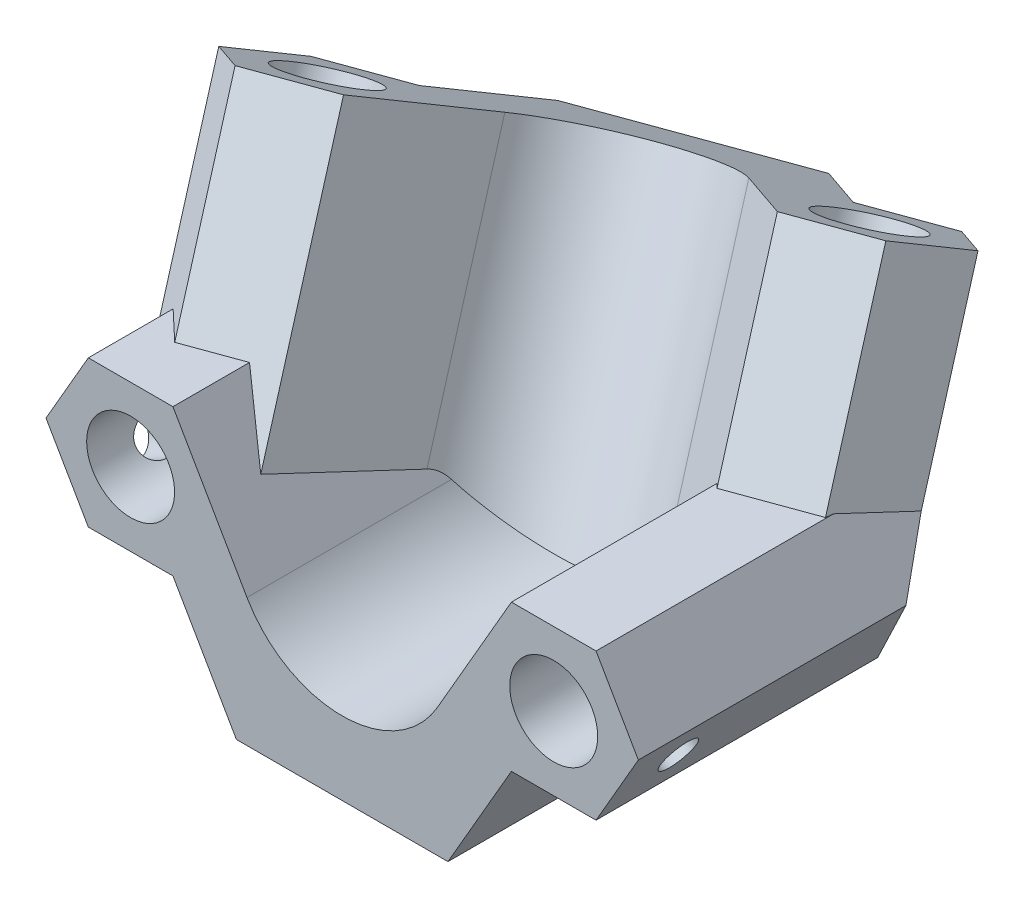
SolidWorks part; units mm, degrees
ref_plane "Front Plane" through (0, 0, 0) normal (0, 0, 1) x (1, 0, 0)
ref_plane "Top Plane" through (0, 0, 0) normal (0, 1, 0) x (1, 0, 0)
ref_plane "Right Plane" through (0, 0, 0) normal (1, 0, 0) x (0, 0, -1)
sketch "Sketch1" plane through (0, 0, 0) normal (0, 1, 0) x (1, 0, 0)
  line L0 (0, 0) -> (0, -10) construction
  line L1 (0, 0) -> (-3.4202, 9.3969) construction
  dimension "D1" = 10
  dimension "D2" = 160
  dimension "D3" = 10
ref_plane "Plane1" through (0, 0, 0) normal (0.9397, 0, -0.342) x (-0.342, 0, -0.9397)
sketch "Sketch2" plane through (0, 0, 0) normal (0.9397, 0, -0.342) x (-0.342, 0, -0.9397)
  line L0 (0, 0) -> (10, 0) construction
  line L1 (0, 0) -> (10, 0) construction
  line L2 (10, 0) -> (10, 17.3205) construction
  line L3 (10, 17.3205) -> (0, 0) construction
  dimension "D1" = 60
  dimension "D2" = 10
sketch "Sketch3" plane through (0, 0, 0) normal (0, 0, 1) x (1, 0, 0)
  line L0 (0, 15) -> (0, -15) construction
  line L1 (13.8564, 6) -> (8.6603, 15) construction
  line L2 (8.6603, 15) -> (0, 15) construction
  line L3 (-8.6603, 15) -> (-13.8564, 6) construction
  line L4 (-13.8564, -6) -> (-8.6603, -15)
  line L5 (-8.6603, -15) -> (8.6603, -15)
  line L6 (8.6603, -15) -> (13.8564, -6)
  line L7 (0, 0) -> (17.3205, 0) construction
  line L8 (13.8564, 6) -> (12.1244, 3) construction
  line L9 (24.2487, 0) -> (20.7846, 6)
  line L10 (20.7846, 6) -> (13.8564, 6)
  line L11 (12.1244, 3) -> (7.7942, -4.5) construction
  line L12 (12.1244, -3) -> (13.8564, -6) construction
  line L13 (13.8564, -6) -> (20.7846, -6)
  line L14 (20.7846, -6) -> (24.2487, 0)
  line L15 (10.3923, 0) -> (12.1244, -3) construction
  line L16 (13.8564, -6) -> (14.3205, -5.1962) construction
  line L17 (15.5205, -3.1177) -> (17.3205, 0) construction
  line L18 (14.3205, -5.1962) -> (15.5205, -3.1177) construction
  line L19 (17.3205, 0) -> (15.5205, 3.1177) construction
  line L20 (15.5205, 3.1177) -> (14.3205, 5.1962) construction
  line L21 (14.3205, 5.1962) -> (13.8564, 6) construction
  line L22 (-13.8564, -6) -> (-20.7846, -6)
  line L23 (-20.7846, -6) -> (-24.2487, 0)
  line L24 (-24.2487, 0) -> (-20.7846, 6)
  line L25 (-20.7846, 6) -> (-13.8564, 6)
  line L26 (-13.8564, 6) -> (-15.5205, 3.1177) construction
  line L27 (-15.5205, 3.1177) -> (-17.3205, 0) construction
  line L28 (-17.3205, 0) -> (-15.5205, -3.1177) construction
  line L29 (-15.5205, -3.1177) -> (-13.8564, -6) construction
  line L30 (-17.3205, 6) -> (-17.3205, -6) construction
  line L31 (-7.7942, -4.5) -> (-13.8564, 6)
  line L32 (7.7942, -4.5) -> (13.8564, 6)
  line L33 (-10.3923, 0) -> (-7.7942, -4.5) construction
  line L34 (0, 15) -> (-8.6603, 15) construction
  line L35 (7.7942, -4.5) -> (10.3923, 0) construction
  line L36 (10.3923, 0) -> (7.7942, -4.5) construction
  circle A0 centre (0, 0) radius 15 construction
  circle A1 centre (17.3205, 0) radius 3.6
  circle A2 centre (17.3205, 0) radius 6 construction
  circle A3 centre (-17.3205, 0) radius 3.6
  arc A4 (-7.7942, -4.5) -> (7.7942, -4.5) centre (0, 0) ccw
  arc A5 (0, 9) -> (-7.7942, -4.5) centre (0, 0) ccw construction
  arc A6 (7.7942, -4.5) -> (0, 9) centre (0, 0) ccw construction
  dimension "D2" = 7.2
  dimension "D4" = 18
  dimension "D1" = 30
  dimension "D3" = 12
extrude "Boss-Extrude1" add sketch "Sketch3" along normal blind 15
ref_plane "Plane2" through (-3.4202, 17.3205, -9.3969) normal (0.171, -0.866, 0.4698) x (-0.9849, -0.1641, 0.056)
sketch "Sketch25" plane through (0, 0, 0) normal (0, 0, -1) x (-1, 0, 0)
  line L0 (-7.7942, -4.5) -> (-13.8564, 6)
  line L1 (-13.8564, 6) -> (-20.7846, 6)
  line L2 (-20.7846, 6) -> (-24.2487, 0)
  line L3 (-24.2487, 0) -> (-20.7846, -6)
  line L4 (-20.7846, -6) -> (-13.8564, -6)
  line L5 (-13.8564, -6) -> (-8.6603, -15)
  line L6 (-8.6603, -15) -> (8.6603, -15)
  line L7 (8.6603, -15) -> (13.8564, -6)
  line L8 (13.8564, -6) -> (20.7846, -6)
  line L9 (20.7846, -6) -> (24.2487, 0)
  line L10 (24.2487, 0) -> (20.7846, 6)
  line L11 (20.7846, 6) -> (13.8564, 6)
  line L12 (13.8564, 6) -> (7.7942, -4.5)
  arc A0 (-7.7942, -4.5) -> (7.7942, -4.5) centre (0, 0) ccw
  arc A1 (-7.7942, -4.5) -> (7.7942, -4.5) centre (0, 0) ccw construction
  arc A2 (7.7942, -4.5) -> (-7.7942, -4.5) centre (0, 0) ccw construction
sketch "Sketch11" plane through (-3.4202, 17.3205, -9.3969) normal (0.171, -0.866, 0.4698) x (-0.9849, -0.1641, 0.056)
  line L0 (-4.9224, -14.1693) -> (4.9224, 14.1693) construction
  line L7 (13.1031, 11.3274) -> (-3.2583, 17.0113)
  line L20 (-3.2583, 17.0113) -> (-11.1201, 10.2148)
  line L21 (-15.058, -1.1206) -> (-13.1031, -11.3274) construction
  line L22 (-4.9224, -14.1693) -> (3.2583, -17.0113) construction
  line L23 (3.2583, -17.0113) -> (11.1201, -10.2148) construction
  line L24 (16.3613, -5.6839) -> (15.7029, -2.2464) construction
  line L25 (2.8419, 8.1807) -> (0, 0) construction
  line L26 (-16.3613, 5.6839) -> (16.3613, -5.6839) construction
  line L27 (15.058, 1.1206) -> (12.4374, -1.1449) construction
  line L28 (-11.1201, 10.2148) -> (-17.6647, 12.4884)
  line L35 (-17.6647, 12.4884) -> (-22.9059, 7.9574)
  line L42 (-22.9059, 7.9574) -> (-21.6026, 1.1529)
  line L43 (-21.6026, 1.1529) -> (-15.058, -1.1206)
  line L44 (-15.058, -1.1206) -> (-5.8859, 6.8085)
  line L45 (-8.8393, -1.6931) -> (-10.4685, 6.8126) construction
  line L46 (22.9059, -7.9574) -> (21.6026, -1.1529)
  line L47 (21.6026, -1.1529) -> (15.058, 1.1206)
  line L48 (5.8859, -6.8085) -> (9.8168, -3.4103) construction
  line L49 (8.8393, 1.6931) -> (11.1201, -10.2148)
  line L50 (11.1201, -10.2148) -> (17.6647, -12.4884)
  line L51 (17.6647, -12.4884) -> (22.9059, -7.9574)
  line L52 (12.4374, -1.1449) -> (5.8859, -6.8085) construction
  line L53 (9.8168, -3.4103) -> (8.8393, 1.6931) construction
  line L54 (15.2326, 0.209) -> (15.058, 1.1206) construction
  line L55 (15.058, 1.1206) -> (13.1031, 11.3274)
  line L56 (15.7029, -2.2464) -> (15.2326, 0.209) construction
  line L57 (13.7136, -7.9728) -> (16.3613, -5.6839) construction
  line L58 (11.8223, -9.6078) -> (13.7136, -7.9728) construction
  line L59 (11.1201, -10.2148) -> (11.8223, -9.6078) construction
  line L60 (-10.4685, 6.8126) -> (-11.1201, 10.2148) construction
  line L61 (-11.8223, 9.6078) -> (-13.6379, 8.0382) construction
  line L62 (-13.6379, 8.0382) -> (-16.3613, 5.6839) construction
  line L63 (-16.3613, 5.6839) -> (-15.6841, 2.1482) construction
  line L64 (-11.1201, 10.2148) -> (-11.8223, 9.6078) construction
  line L65 (-15.6841, 2.1482) -> (-15.2326, -0.209) construction
  line L66 (-15.2326, -0.209) -> (-15.058, -1.1206) construction
  line L67 (-5.8859, 6.8085) -> (-9.8168, 3.4103) construction
  line L68 (-9.8168, 3.4103) -> (-8.8393, -1.6931) construction
  line L69 (-13.1031, -11.3274) -> (-4.9224, -14.1693) construction
  circle A0 centre (0, 0) radius 15 construction
  circle A2 centre (-16.3613, 5.6839) radius 6 construction
  circle A4 centre (-16.3613, 5.6839) radius 3.6
  circle A5 centre (16.3613, -5.6839) radius 6 construction
  circle A6 centre (16.3613, -5.6839) radius 3.5
  arc A7 (8.8393, 1.6931) -> (-5.8859, 6.8085) centre (0, 0) ccw
  arc A8 (-2.9534, -8.5016) -> (8.8393, 1.6931) centre (0, 0) ccw construction
  arc A9 (-5.8859, 6.8085) -> (-2.9534, -8.5016) centre (0, 0) ccw construction
  dimension "D2" = 12
  dimension "D4" = 12
  dimension "D3" = 7.2
  dimension "D5" = 7
  dimension "D6" = 18
  dimension "D1" = 30
extrude "Boss-Extrude6" add sketch "Sketch11" along normal up to surface (33.8564 mm away) up to face at (0, -15, 7.5)
sketch "Sketch22" plane through (0, 0, 15) normal (0, 0, 1) x (1, 0, 0)
  line L0 (8.6603, -15) -> (-7.1843, -15)
  line L1 (-9.2861, -6.9129) -> (-7.1843, -15) construction
  circle A0 centre (-17.3205, 0) radius 3.6
  arc A1 (-15.6091, -3.1672) -> (-17.8643, 3.5587) centre (-17.3205, 0) ccw construction
  circle A2 centre (17.3205, 0) radius 3.6
  circle A3 centre (17.3205, 0) radius 3.6 construction
  circle A4 centre (0, 0) radius 9
  arc A5 (-7.7942, -4.5) -> (7.7942, -4.5) centre (0, 0) ccw construction
  arc M23 (7.7942, -4.5) -> (-7.7942, -4.5) centre (0, 0) cw
extrude "Cut-Extrude5" cut sketch "Sketch22" against normal up to surface (15 mm away) contours A4 M23 | A0 | A2 region at (0, 0, 15) up to face at (-19.4691, -1.9575, 0)
sketch "Sketch23" plane through (0, 0, 0) normal (0, 1, 0) x (1, 0, 0)
  line L0 (24.2487, -15) -> (24.2487, 0) construction
  line L1 (-24.2487, -15) -> (24.2487, -15)
  line L2 (-24.2487, -15) -> (-24.2487, -21.7571)
  line L3 (-24.2487, -21.7571) -> (24.2487, -21.7571)
  line L4 (24.2487, -15) -> (24.2487, -21.7571)
extrude "Cut-Extrude6" cut sketch "Sketch23" against normal through all both and the other way through all
sketch "Sketch24" plane through (0, 0, 15) normal (0, 0, 1) x (1, 0, 0)
  line L0 (-24.2487, 0) -> (-20.7846, -6)
  line L1 (-20.7846, -6) -> (-13.8564, -6)
  line L2 (-13.8564, -6) -> (-8.6603, -15)
  line L3 (-8.6603, -15) -> (-19.6596, -15)
  line L4 (-19.6596, -15) -> (-24.2487, 0)
  line L5 (8.6603, -15) -> (13.8564, -6)
  line L6 (13.8564, -6) -> (20.7846, -6)
  line L7 (20.7846, -6) -> (24.2487, 0)
  line L8 (24.2487, 0) -> (25.7483, -15)
  line L9 (25.7483, -15) -> (8.6603, -15)
extrude "Cut-Extrude7" cut sketch "Sketch24" against normal through all both and the other way through all
extrude "Boss-Extrude7" add sketch "Sketch25" along normal up to surface (18.5042 mm away) up to face at (-6.3157, -3.7874, -13.8064)
sketch "Sketch26" plane through (-3.4202, 17.3205, -9.3969) normal (-0.171, 0.866, -0.4698) x (0.9853, 0.1503, -0.0815)
  line L0 (-12.769, 11.7026) -> (-15.0192, 1.5568)
  line L1 (-15.0192, 1.5568) -> (-24.01, -1.2771)
  line L2 (-25.1148, -13.1846) -> (-23.1081, 8.4437) construction
  line L3 (-24.01, -1.2771) -> (-23.1081, 8.4437)
  line L4 (-23.1081, 8.4437) -> (-12.769, 11.7026)
  line L5 (3.7502, 16.9096) -> (11.4117, 9.8881)
  line L6 (11.4117, 9.8881) -> (18.0194, 11.9709)
  line L7 (18.0194, 11.9709) -> (24.4549, 6.0728)
  line L8 (22.6683, -13.1846) -> (26.1144, 23.959) construction
  line L9 (24.4549, 6.0728) -> (26.1144, 23.959)
  line L10 (26.1144, 23.959) -> (3.7502, 16.9096)
extrude "Cut-Extrude8" cut sketch "Sketch26" against normal through all both and the other way through all
sketch "Sketch27" plane through (-18.1865, -10.5, 0) normal (-0.866, -0.5, 0) x (0, 0, 1)
  line L0 (15, 8.6603) -> (2.6658, 8.6603) construction
  line L1 (15, 12.1244) -> (15, 5.1962) construction
  line L2 (1.453, 12.1244) -> (3.8786, 5.1962) construction
  line L3 (10, 12.1244) -> (10, 5.1962) construction
  line L4 (15, 12.1244) -> (1.453, 12.1244) construction
  line L5 (15, 5.1962) -> (3.8786, 5.1962) construction
  circle A0 centre (10, 8.6603) radius 1.5
  dimension "D1" = 3
  dimension "D2" = 5
extrude "Cut-Extrude9" cut sketch "Sketch27" against normal up to surface and the other way through all up to face at (-17.3205, 0, 0.7511)
sketch "Sketch28" plane through (18.1865, -10.5, 0) normal (0.866, -0.5, 0) x (0, 0, -1)
  line L0 (-15, 8.6603) -> (7.4822, 8.6603) construction
  line L1 (-15, 5.1962) -> (-15, 12.1244) construction
  line L2 (8.0554, 5.1962) -> (6.909, 12.1244) construction
  circle A0 centre (-10, 8.6603) radius 1.5
  dimension "D1" = 3
  dimension "D2" = 5
extrude "Cut-Extrude10" cut sketch "Sketch28" against normal up to surface (2.7274 mm away) up to face at (20.9205, 0, 0)
sketch "Sketch29" plane through (-20.1998, -5.25, -2.3247) normal (-0.9619, -0.25, -0.1107) x (-0.1071, -0.0278, 0.9939)
  line L0 (-1.8237, 21.7181) -> (5.4703, 8.1224) construction
  line L1 (1.2289, 23.3557) -> (-4.8762, 20.0804) construction
  line L2 (1.2869, 8.5925) -> (9.6536, 7.6523) construction
  circle A0 centre (0.5401, 17.3121) radius 1.5
  dimension "D1" = 3
  dimension "D2" = 5
extrude "Cut-Extrude11" cut sketch "Sketch29" against normal up to surface (2.5726 mm away) contours A0 up to face at (-19.6962, 15.6515, -6.5494)
sketch "Sketch30" plane through (13.9797, -5.25, -14.765) normal (0.6657, -0.25, -0.7031) x (-0.7462, -0.223, -0.6272)
  line L0 (-3.8464, 21.4524) -> (-9.4928, -2.5305) construction
  line L1 (-0.4745, 20.6585) -> (-7.2183, 22.2463) construction
  line L2 (-9.1192, -2.9545) -> (-13.7614, 2.3146) construction
  circle A0 centre (-4.9923, 16.5855) radius 1.5
  dimension "D1" = 3
  dimension "D2" = 5
extrude "Cut-Extrude12" cut sketch "Sketch30" against normal up to surface (2.6593 mm away) up to face at (12.8558, 15.6038, -18.4852)
sketch "Sketch31" plane through (-4.443, -7.5, -12.207) normal (-0.2962, -0.5, -0.8138) x (-0.9551, 0.1551, 0.2524)
  line L0 (3.5809, 19.6768) -> (-1.5506, -8.5203) construction
  line L1 (12.1012, 18.1262) -> (-4.9394, 21.2274) construction
  line L2 (-10.0709, -6.9697) -> (4.4154, -9.606) construction
  line L3 (-4.0102, -8.0727) -> (-2.5778, -0.202)
  line L4 (-2.5778, -0.202) -> (2.3414, -1.0972)
  line L5 (2.3414, -1.0972) -> (0.909, -8.9679)
  line L6 (0.909, -8.9679) -> (-4.0102, -8.0727)
  point P8 (-0.1182, -0.6496)
  dimension "D1" = 5
  dimension "D2" = 8
extrude "Boss-Extrude8" add sketch "Sketch31" along normal blind 10
sketch "Sketch32" plane through (2.3492, 0, -0.8551) normal (0.9397, 0, -0.342) x (-0.342, 0, -0.9397)
  line L0 (19.3205, -16.5359) -> (10.6603, -11.5359) construction
  line L3 (21.3205, -13.0718) -> (17.3205, -20) construction
  line L4 (8.6603, -15) -> (22.9904, 9.8205) construction
  circle A0 centre (17.1554, -15.2859) radius 1.5
  dimension "D1" = 3
  dimension "D2" = 2.5
extrude "Cut-Extrude13" cut sketch "Sketch32" against normal through all
fillet "Fillet1" radius 3 1 edges at (-7.292, -13.0718, -20.0347) type face fillet first side face at (-6.608, -16.5359, -18.1553) second side face at (-5.8111, -10.5718, -15.9657)
fillet "Fillet2" radius 3 1 edges at (-5.924, -20, -16.276) type face fillet first side face at (-6.3515, -17.8349, -17.4506) second side face at (-4.443, -17.5, -12.207)
sketch "Sketch33" plane through (-4.443, -7.5, -12.207) normal (-0.2962, -0.5, -0.8138) x (-0.9551, 0.1551, 0.2524)
  line L0 (-1.5506, -8.5203) -> (20.9683, 115.2197) construction
  line L1 (-4.0102, -8.0727) -> (0.909, -8.9679) construction
  line L2 (12.1012, 18.1262) -> (-4.9394, 21.2274) construction
